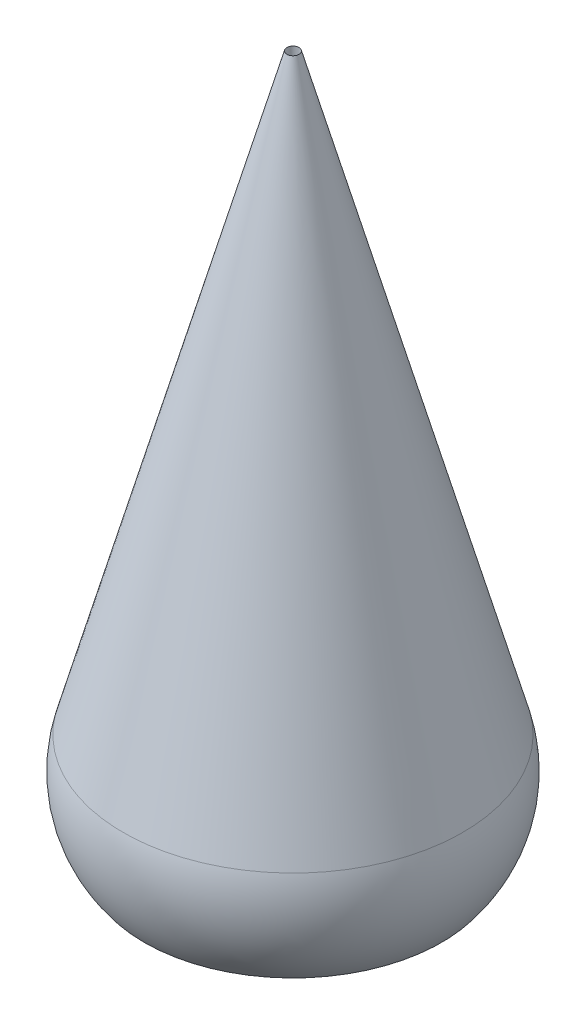
SolidWorks part; units mm, degrees
material "PUR"
ref_plane "Front Plane" through (0, 0, 0) normal (0, 0, 1) x (1, 0, 0)
ref_plane "Top Plane" through (0, 0, 0) normal (0, 1, 0) x (1, 0, 0)
ref_plane "Right Plane" through (0, 0, 0) normal (1, 0, 0) x (0, 0, -1)
sketch "Sketch3" plane through (0, 0, 0) normal (0, 0, 1) x (1, 0, 0)
  line L0 (0, 0) -> (0, 60)
  line L1 (0, 60) -> (16.6016, 0)
  line L2 (16.6016, 0) -> (12.4056, 0)
  line L3 (12.4056, 0) -> (0, 44.8352)
  line L4 (0, 44.8352) -> (0, 60)
revolve "Revolve1" add sketch "Sketch3" angle 360 about L0 region at (7.3024, 26.3916, 0)
fillet "Fillet1" radius 10 1 edges at (0, 0, -16.6016)
sketch "Sketch5" plane through (0, 0, 0) normal (0, 1, 0) x (1, 0, 0)
  circle A0 centre (0, 0) radius 0.5
extrude "Boss-Extrude1" add sketch "Sketch5" along normal blind 60
sketch "Sketch7" plane through (0, 60, 0) normal (0, 1, 0) x (1, 0, 0)
  circle A0 centre (0, 0) radius 0.5
extrude "Cut-Extrude1" cut sketch "Sketch7" against normal blind 5
